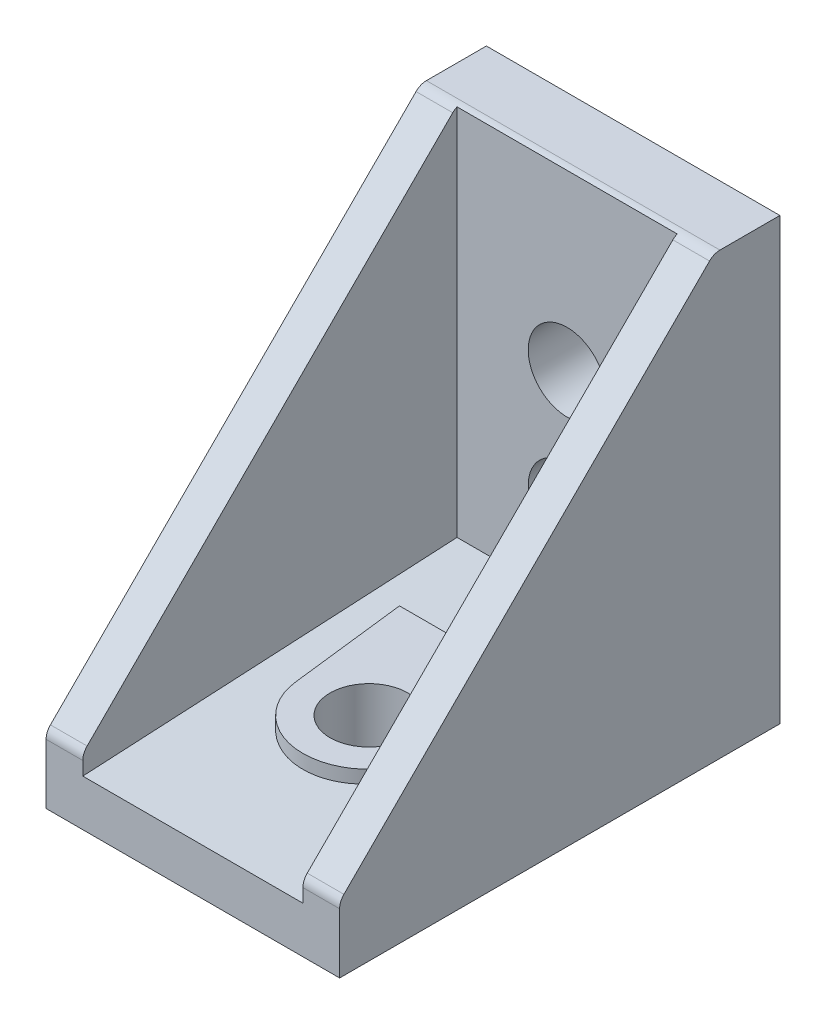
SolidWorks part; units mm, degrees
material "356.0-T6 Permanent Mold cast (SS)"
ref_plane "Front Plane" through (0, 0, 0) normal (0, 0, 1) x (1, 0, 0)
ref_plane "Top Plane" through (0, 0, 0) normal (0, 1, 0) x (1, 0, 0)
ref_plane "Right Plane" through (0, 0, 0) normal (1, 0, 0) x (0, 0, -1)
ref_plane "Plane1" through (0, 0, 0) normal (1, 0, 0) x (0, 0, -1)
sketch "Sketch1" plane through (0, 0, 0) normal (1, 0, 0) x (0, 0, -1)
  line L0 (-30, 0) -> (0, 0)
  line L1 (0, 0) -> (0, 30)
  line L2 (0, 30) -> (-4.0858, 30)
  line L3 (-4.7929, 29.7071) -> (-29.7071, 4.7929)
  line L4 (-30, 4.0858) -> (-30, 0)
  arc A0 (-4.0858, 30) -> (-4.7929, 29.7071) centre (-4.0858, 29) ccw
  arc A1 (-29.7071, 4.7929) -> (-30, 4.0858) centre (-29, 4.0858) ccw
extrude "Boss-Extrude1" add sketch "Sketch1" against normal blind 10 and the other way blind 10
ref_plane "Plane2" through (0, 0, 0) normal (1, 0, 0) x (0, 0, -1)
sketch "Sketch2" plane through (0, 0, 0) normal (1, 0, 0) x (0, 0, -1)
  line L0 (-34.5, 2.9278) -> (-4.5, 4.5)
  line L1 (-4.5, 4.5) -> (-4.5, 34.5)
  line L2 (-4.5, 34.5) -> (-34.5, 34.5)
  line L3 (-34.5, 34.5) -> (-34.5, 2.9278)
extrude "Cut-Extrude1" cut sketch "Sketch2" against normal blind 7.5 and the other way blind 7.5
ref_plane "Plane3" through (0, 4.5, 0) normal (0, 1, 0) x (1, 0, 0)
sketch "Sketch3" plane through (0, 4.5, 0) normal (0, 1, 0) x (1, 0, 0)
  line L0 (-5.4209, -10.5) -> (-4.4687, -18.5299)
  line L1 (4.4687, -18.5299) -> (5.4209, -10.5)
  line L2 (5.4209, -10.5) -> (-5.4209, -10.5)
  arc A0 (-4.4687, -18.5299) -> (4.4687, -18.5299) centre (0, -18) ccw
extrude "Boss-Extrude2" add sketch "Sketch3" against normal blind 2.25
ref_plane "Plane4" through (0, 0, 0) normal (0, 0, 1) x (1, 0, 0)
sketch "Sketch4" plane through (0, 0, 0) normal (0, 0, 1) x (1, 0, 0)
  circle A0 centre (0, 18) radius 2.65
extrude "Cut-Extrude2" cut sketch "Sketch4" along normal blind 4.5
ref_plane "Plane5" through (0, 0, 0) normal (0, 0, 1) x (1, 0, 0)
sketch "Sketch5" plane through (0, 0, 0) normal (0, 0, 1) x (1, 0, 0)
  circle A0 centre (0, 10) radius 2.65
extrude "Cut-Extrude3" cut sketch "Sketch5" along normal blind 4.5
ref_plane "Plane6" through (0, 0, 0) normal (0, 1, 0) x (1, 0, 0)
sketch "Sketch6" plane through (0, 0, 0) normal (0, 1, 0) x (1, 0, 0)
  circle A0 centre (0, -18) radius 2.65
extrude "Cut-Extrude4" cut sketch "Sketch6" along normal blind 4.5
ref_plane "Plane7" through (0, 0, 0) normal (0, 1, 0) x (1, 0, 0)
sketch "Sketch7" plane through (0, 0, 0) normal (0, 1, 0) x (1, 0, 0)
  line L0 (-10, 0) -> (-10, -30)
  line L1 (-10, -30) -> (10, -30)
  line L2 (10, -30) -> (10, 0)
  line L3 (10, 0) -> (-10, 0)
extrude "Boss-Extrude3" add sketch "Sketch7" against normal blind 1
ref_plane "Plane8" through (0, 0, 0) normal (0, 1, 0) x (1, 0, 0)
sketch "Sketch8" plane through (0, 0, 0) normal (0, 1, 0) x (1, 0, 0)
  line L0 (-10, 0) -> (-10, -30)
  line L1 (-10, -30) -> (10, -30)
  line L2 (10, -30) -> (10, 0)
  line L3 (10, 0) -> (-10, 0)
  line L4 (-2.7, -11) -> (2.7, -11)
  line L5 (3, -10.7) -> (3, -5.3)
  line L6 (2.7, -5) -> (-2.7, -5)
  line L7 (-3, -5.3) -> (-3, -10.7)
  line L8 (-2.7, -27) -> (2.7, -27)
  line L9 (3, -26.7) -> (3, -24.3)
  line L10 (2.7, -24) -> (-2.7, -24)
  line L11 (-3, -24.3) -> (-3, -26.7)
  arc A0 (-3, -10.7) -> (-2.7, -11) centre (-2.7, -10.7) ccw
  arc A1 (2.7, -11) -> (3, -10.7) centre (2.7, -10.7) ccw
  arc A2 (3, -5.3) -> (2.7, -5) centre (2.7, -5.3) ccw
  arc A3 (-2.7, -5) -> (-3, -5.3) centre (-2.7, -5.3) ccw
  arc A4 (-3, -26.7) -> (-2.7, -27) centre (-2.7, -26.7) ccw
  arc A5 (2.7, -27) -> (3, -26.7) centre (2.7, -26.7) ccw
  arc A6 (3, -24.3) -> (2.7, -24) centre (2.7, -24.3) ccw
  arc A7 (-2.7, -24) -> (-3, -24.3) centre (-2.7, -24.3) ccw
extrude "Cut-Extrude5" cut sketch "Sketch8" against normal blind 1
ref_plane "Plane9" through (0, 0, 0) normal (0, 0, 1) x (1, 0, 0)
sketch "Sketch9" plane through (0, 0, 0) normal (0, 0, 1) x (1, 0, 0)
  line L0 (-10, 0) -> (10, 0)
  line L1 (10, 0) -> (10, 30)
  line L2 (10, 30) -> (-10, 30)
  line L3 (-10, 30) -> (-10, 0)
extrude "Boss-Extrude4" add sketch "Sketch9" against normal blind 1
ref_plane "Plane10" through (0, 0, 0) normal (0, 0, 1) x (1, 0, 0)
sketch "Sketch10" plane through (0, 0, 0) normal (0, 0, 1) x (1, 0, 0)
  line L0 (-10, 0) -> (10, 0)
  line L1 (10, 0) -> (10, 30)
  line L2 (10, 30) -> (-10, 30)
  line L3 (-10, 30) -> (-10, 0)
  line L4 (0.5, 7) -> (2, 7)
  line L5 (3, 8) -> (3, 9.5)
  line L6 (3, 9.5) -> (2.6024, 9.5)
  line L7 (0.5, 7.3976) -> (0.5, 7)
  line L8 (0.5, 13) -> (0.5, 12.6024)
  line L9 (2.6024, 10.5) -> (3, 10.5)
  line L10 (3, 10.5) -> (3, 12)
  line L11 (2, 13) -> (0.5, 13)
  line L12 (-3, 9.5) -> (-3, 8)
  line L13 (-2, 7) -> (-0.5, 7)
  line L14 (-0.5, 7) -> (-0.5, 7.3976)
  line L15 (-2.6024, 9.5) -> (-3, 9.5)
  line L16 (-3, 10.5) -> (-2.6024, 10.5)
  line L17 (-0.5, 12.6024) -> (-0.5, 13)
  line L18 (-0.5, 13) -> (-2, 13)
  line L19 (-3, 12) -> (-3, 10.5)
  arc A0 (2, 7) -> (3, 8) centre (2, 8) ccw
  arc A1 (2.6024, 9.5) -> (0.5, 7.3976) centre (0, 10) cw
  arc A2 (0.5, 12.6024) -> (2.6024, 10.5) centre (0, 10) cw
  arc A3 (3, 12) -> (2, 13) centre (2, 12) ccw
  arc A4 (-3, 8) -> (-2, 7) centre (-2, 8) ccw
  arc A5 (-0.5, 7.3976) -> (-2.6024, 9.5) centre (0, 10) cw
  arc A6 (-2.6024, 10.5) -> (-0.5, 12.6024) centre (0, 10) cw
  arc A7 (-2, 13) -> (-3, 12) centre (-2, 12) ccw
extrude "Cut-Extrude6" cut sketch "Sketch10" against normal blind 1
